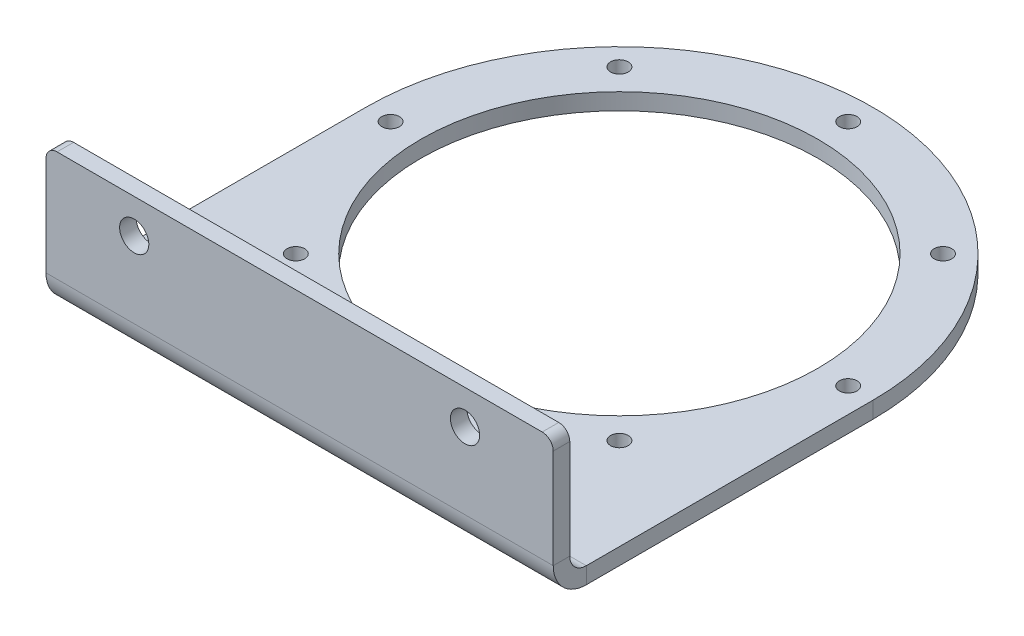
SolidWorks part; units mm, degrees
note: The reader was unsure of these and kept them because the rebuilt part matched: flange length of "Edge-Flange1".
material "3.3549 (EN-AW 5182)"
ref_plane "Front Plane" through (0, 0, 0) normal (0, 0, 1) x (1, 0, 0)
ref_plane "Top Plane" through (0, 0, 0) normal (0, 1, 0) x (1, 0, 0)
ref_plane "Right Plane" through (0, 0, 0) normal (1, 0, 0) x (0, 0, -1)
sketch "Sketch1" plane through (0, 0, 0) normal (0, 1, 0) x (1, 0, 0)
  line L0 (0, -44.7868) -> (0, 44.7868) construction
  line L1 (-46, 0) -> (-46, -55)
  line L2 (-46, -55) -> (46, -55)
  line L3 (46, -55) -> (46, 0)
  line L4 (-44.2539, 0) -> (44.2539, 0) construction
  circle A0 centre (0, 0) radius 36
  arc A1 (46, 0) -> (-46, 0) centre (0, 0) ccw
  circle A2 centre (0, 41.5) radius 1
  circle A3 centre (29.3449, 29.3449) radius 1
  circle A4 centre (41.5, 0) radius 1
  circle A5 centre (29.3449, -29.3449) radius 1
  circle A6 centre (0, -41.5) radius 1
  circle A7 centre (-29.3449, -29.3449) radius 1
  circle A8 centre (-41.5, 0) radius 1
  circle A9 centre (-29.3449, 29.3449) radius 1
  point P10 (0, -55)
  point P25 (0, 0)
  dimension "D1" = 92
  dimension "D2" = 72
  dimension "D3" = 2
  dimension "D4" = 41.5
  dimension "D7" = 55
  dimension "D5" = 8
base flange "Base-Flange1" sketch "Sketch1" thickness 3 reverse thickness direction no parameters "D1"=3
edge flange "Edge-Flange1" sketch "Sketch8" flange angle 90 flange length 26 flange position material outside bend radius 3 thickness 3 relief rectangular parameters "D1"=2.5, "D6"=10
sketch "Sketch8" plane through (0, 0, 55) normal (0, 0, 1) x (1, 0, 0)
  line L0 (-46, 0) -> (46, 0) construction
  line L1 (-46, 0) -> (46, 0)
  line L2 (-46, 0) -> (-46, 23)
  line L3 (-46, 23) -> (46, 23)
  line L4 (46, 23) -> (46, 0)
  line L5 (0, -44.7868) -> (0, 44.7868) construction
  circle A0 centre (-30, 16.8) radius 1
  circle A1 centre (30, 16.8) radius 1
  dimension "D2" = 16.8
  dimension "D5" = 2
  dimension "D1" = 23
  dimension "D3" = 30
  dimension "D4" = 30
bend "EdgeBend1" bend radius 3 bend angle 90 parameters "D5"=1
fillet "Fillet1" radius 2 2 edges at (-46, 23, 56.5) (46, 23, 56.5)
sketch "Sketch12" plane through (0, 0, 0) normal (0, 1, 0) x (1, 0, 0)
  point P0 (0, 41.5)
  point P3 (29.3449, 29.3449)
  point P6 (41.5, 0)
  point P9 (29.3449, -29.3449)
  point P12 (0, -41.5)
  point P15 (-29.3449, -29.3449)
  point P18 (-41.5, 0)
  point P21 (-29.3449, 29.3449)
hole_wizard "M3 Clearance Hole1" positions "Sketch12" profile "Sketch11" hole size "M3" standard "ANSI Metric"
sketch "Sketch11" plane through (0, 0, -41.5) normal (1, 0, 0) x (0, 0, 1)
  line L0 (0, 0) -> (0, 136.9614)
  line L1 (0, 136.9614) -> (1.6, 136)
  line L2 (1.6, 136) -> (1.6, 0)
  line L5 (1.6, 0) -> (0, 0)
  line L10 (0, 136.9614) -> (-1.6, 136) construction
  line L11 (0, -6.35) -> (0, 107.95) construction
  dimension "Hole Dia." = 3.2
  dimension "Hole Depth" = 136
  dimension "Drill Angle" = 118
sketch "Sketch16" plane through (0, 0, 58) normal (0, 0, 1) x (1, 0, 0)
  point P0 (30, 16.8)
  point P3 (-30, 16.8)
hole_wizard "M5 Clearance Hole1" positions "Sketch16" profile "Sketch15" hole size "M5" standard "ANSI Metric"
sketch "Sketch15" plane through (30, 16.8, 58) normal (1, 0, 0) x (0, -1, 0)
  line L0 (0, 0) -> (0, 137.5923)
  line L1 (0, 137.5923) -> (2.65, 136)
  line L2 (2.65, 136) -> (2.65, 0)
  line L5 (2.65, 0) -> (0, 0)
  line L10 (0, 137.5923) -> (-2.65, 136) construction
  line L11 (0, -6.35) -> (0, 107.95) construction
  dimension "Hole Dia." = 5.3
  dimension "Hole Depth" = 136
  dimension "Drill Angle" = 118
sketch "Bend-Lines1" [suppressed] plane through (0, 0, 0) normal (0, 1, 0) x (1, 0, 0)
sketch "Bounding-Box1" [suppressed] plane through (0, 0, 0) normal (0, 1, 0) x (1, 0, 0)
sheet metal parameters "Sheet-Metal8" thickness 3 parameters "D1"=1.6
flat pattern "Flat-Pattern8" [suppressed]
sketch "Bend-Lines2" plane through (0, 0, 0) normal (0, 1, 0) x (1, 0, 0)
sketch3d "Bounding-Box2" [suppressed]
  line L0 (45, 45, 0) -> (45, -50, 0) construction
  line L1 (-45, 45, 0) -> (-45, -50, 0) construction
  line L2 (45, 45, 0) -> (-45, 45, 0) construction
  line L3 (45, -50, 0) -> (-45, -50, 0) construction
sheet metal parameters "Sheet-Metal9" thickness 3 parameters "D1"=1.6
flat pattern "Flat-Pattern8"
sketch "Bend-Lines2" plane through (0, 0, 0) normal (0, 1, 0) x (1, 0, 0)
  line L0 (-45, -50.8347) -> (45, -50.8347) construction
  line L1 (-45, -50.8347) -> (45, -50.8347) construction
sketch3d "Bounding-Box2" [suppressed]
  line L0 (45, 45, 0) -> (45, -63.6695, 0) construction
  line L1 (-45, 45, 0) -> (-45, -63.6695, 0) construction
  line L2 (45, 45, 0) -> (-45, 45, 0) construction
  line L3 (45, -63.6695, 0) -> (-45, -63.6695, 0) construction
bend of the flat pattern "Flatten-<EdgeBend1>1"
sheet metal parameters "Sheet-Metal11" thickness 3 parameters "D1"=1.6
flat pattern "Flat-Pattern8"
sketch "Bend-Lines2" plane through (0, 0, 0) normal (0, 1, 0) x (1, 0, 0)
  line L0 (-46, -55.6416) -> (46, -55.6416) construction
  line L1 (-46, -55.6416) -> (46, -55.6416) construction
sketch3d "Bounding-Box2" [suppressed]
  line L0 (-46, 46, 0) -> (-46, -79.2832, 0) construction
  line L1 (46, 46, 0) -> (46, -79.2832, 0) construction
  line L2 (-46, 46, 0) -> (46, 46, 0) construction
  line L3 (-46, -79.2832, 0) -> (46, -79.2832, 0) construction
bend of the flat pattern "Flatten-<EdgeBend1>1"
sheet metal parameters "Sheet-Metal12" thickness 3 parameters "D1"=1.6
flat pattern "Flat-Pattern8"
sketch "Bend-Lines2" plane through (0, 0, 0) normal (0, 1, 0) x (1, 0, 0)
  line L0 (-46, -55.1) -> (46, -55.1) construction
  line L1 (-46, -55.1) -> (46, -55.1) construction
sketch3d "Bounding-Box2" [suppressed]
  line L0 (-46, 46, 0) -> (-46, -78.2, 0) construction
  line L1 (46, 46, 0) -> (46, -78.2, 0) construction
  line L2 (-46, 46, 0) -> (46, 46, 0) construction
  line L3 (-46, -78.2, 0) -> (46, -78.2, 0) construction
bend of the flat pattern "Flatten-<EdgeBend1>1"
